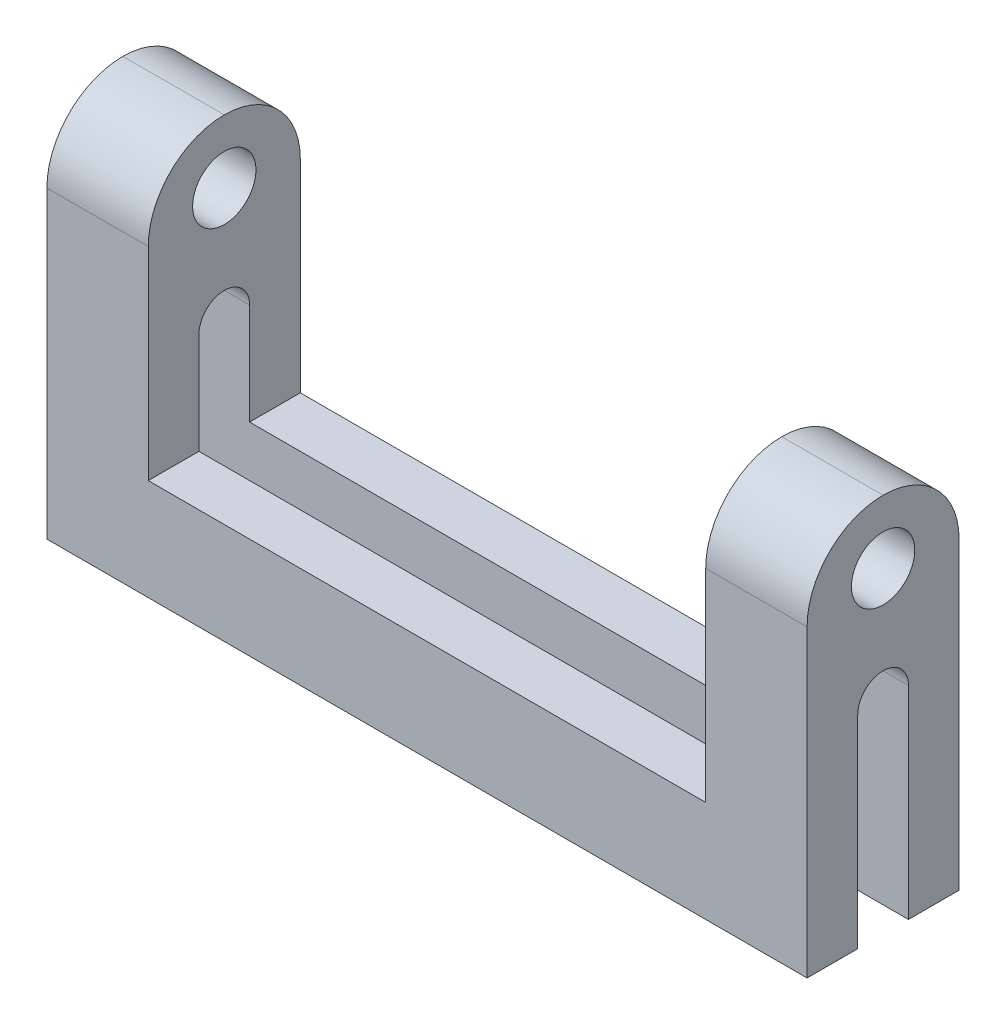
SolidWorks part; units mm, degrees
ref_plane "Front Plane" through (0, 0, 0) normal (0, 0, 1) x (1, 0, 0)
ref_plane "Top Plane" through (0, 0, 0) normal (0, 1, 0) x (1, 0, 0)
ref_plane "Right Plane" through (0, 0, 0) normal (1, 0, 0) x (0, 0, -1)
sketch "Sketch1" plane through (0, 0, 0) normal (0, 1, 0) x (1, 0, 0)
  line L1 (-30, -6) -> (30, -6)
  line L2 (-30, -6) -> (-30, 6)
  line L3 (-30, 6) -> (30, 6)
  line L4 (30, -6) -> (30, 6)
  line L5 (-30, -6) -> (30, 6) construction
  line L6 (-30, 6) -> (30, -6) construction
  point P0 (0, 0)
  dimension "D1" = 60
  dimension "D2" = 12
extrude "Boss-Extrude1" add sketch "Sketch1" along normal blind 8
sketch "Sketch2" plane through (0, 8, 0) normal (0, 1, 0) x (1, 0, 0)
  line L0 (-30, -6) -> (30, -6) construction
  line L1 (-30, 6) -> (-22, 6)
  line L2 (-30, 6) -> (-30, -6)
  line L3 (-30, -6) -> (-22, -6)
  line L4 (-22, 6) -> (-22, -6)
  line L6 (30, 6) -> (22, 6)
  line L7 (30, 6) -> (30, -6)
  line L8 (30, -6) -> (22, -6)
  line L9 (22, 6) -> (22, -6)
  dimension "D1" = 8
  dimension "D2" = 8
extrude "Boss-Extrude2" add sketch "Sketch2" along normal blind 22
sketch "Sketch3" plane through (-30, 0, 0) normal (-1, 0, 0) x (0, 0, 1)
  line L0 (-6, 0) -> (6, 0) construction
  circle A0 centre (0, 25) radius 2.5
  dimension "D2" = 5
  dimension "D1" = 25
extrude "Cut-Extrude1" cut sketch "Sketch3" against normal through all
fillet "Fillet1" radius 6 4 edges at (-26, 30, 6) (26, 30, 6) (26, 30, -6) (-26, 30, -6)
sketch "Sketch5" plane through (0, 0, 0) normal (0, -1, 0) x (1, 0, 0)
  line L0 (30, 6) -> (30, -6) construction
  line L1 (-30, -2) -> (30, -2)
  line L2 (-30, -2) -> (-30, 2)
  line L3 (-30, 2) -> (30, 2)
  line L4 (30, -2) -> (30, 2)
  line L5 (-30, -2) -> (30, 2) construction
  line L6 (-30, 2) -> (30, -2) construction
  point P0 (0, 0)
  dimension "D1" = 4
extrude "Cut-Extrude2" cut sketch "Sketch5" against normal blind 18
fillet "Fillet2" radius 2 4 edges at (-26, 18, 2) (-26, 18, -2) (26, 18, -2) (26, 18, 2)
